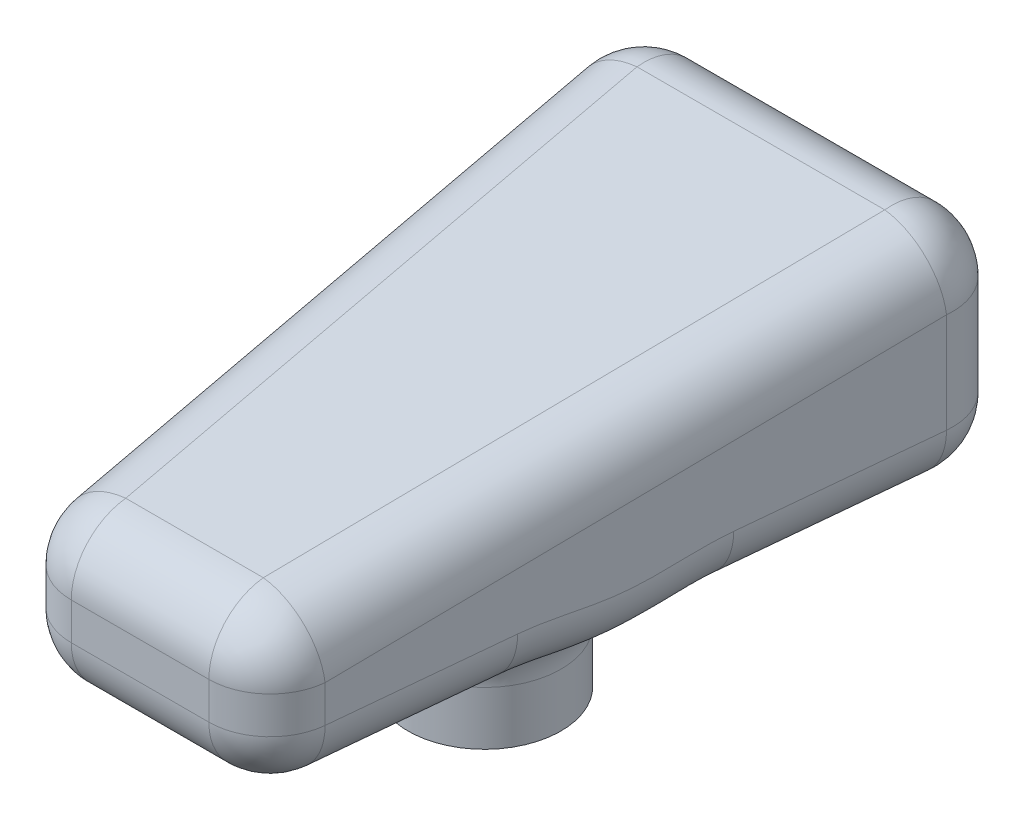
SolidWorks part; units mm, degrees
ref_plane "Front Plane" through (0, 0, 0) normal (0, 0, 1) x (1, 0, 0)
ref_plane "Top Plane" through (0, 0, 0) normal (0, 1, 0) x (1, 0, 0)
ref_plane "Right Plane" through (0, 0, 0) normal (1, 0, 0) x (0, 0, -1)
sketch "Sketch1" plane through (0, 0, 0) normal (0, 1, 0) x (1, 0, 0)
  circle A0 centre (0, 0) radius 25.4
  dimension "D1" = 50.8
extrude "Boss-Extrude1" add sketch "Sketch1" along normal blind 38.1
sketch "Sketch2" plane through (0, 38.1, 0) normal (0, 1, 0) x (1, 0, 0)
  line L1 (-63.5, -114.3) -> (63.5, -114.3)
  line L2 (-63.5, -114.3) -> (-63.5, 114.3)
  line L3 (-63.5, 114.3) -> (63.5, 114.3)
  line L4 (63.5, -114.3) -> (63.5, 114.3)
  line L5 (-63.5, -114.3) -> (63.5, 114.3) construction
  line L6 (-63.5, 114.3) -> (63.5, -114.3) construction
  point P0 (0, 0)
  dimension "D1" = 228.6
  dimension "D2" = 127
extrude "Boss-Extrude2" add sketch "Sketch2" along normal blind 76.2
fillet "Fillet1" radius 20.32 1 edges at (0, 38.1, 25.4)
sketch "Sketch3" plane through (63.5, 0, 0) normal (1, 0, 0) x (0, 0, -1)
  line L0 (114.3, 114.3) -> (-114.3, 114.3)
  line L1 (-114.3, 114.3) -> (-114.3, 88.9)
  line L2 (-114.3, 114.3) -> (-114.3, 38.1) construction
  line L3 (-114.3, 88.9) -> (114.3, 114.3)
  dimension "D1" = 25.4
extrude "Cut-Extrude1" cut sketch "Sketch3" against normal up to next
sketch "Sketch5" plane through (0, 38.1, 0) normal (0, -1, 0) x (1, 0, 0)
  line L0 (63.5, 114.3) -> (63.5, -114.3)
  line L1 (63.5, -114.3) -> (41.275, 114.3)
  line L2 (-63.5, 114.3) -> (63.5, 114.3) construction
  line L3 (41.275, 114.3) -> (63.5, 114.3)
  line L4 (-63.5, -114.3) -> (-63.5, 114.3)
  line L5 (-63.5, 114.3) -> (-41.275, 114.3)
  line L6 (-41.275, 114.3) -> (-63.5, -114.3)
  dimension "D1" = 22.225
  dimension "D2" = 22.225
extrude "Cut-Extrude3" cut sketch "Sketch5" against normal up to next
fillet "Fillet2" radius 20.32 12 edges at (41.275, 63.5, 114.3) (-41.275, 63.5, 114.3) (-63.5, 76.2, -114.3) (63.5, 76.2, -114.3) (52.3875, 38.1, 0) (0, 38.1, -114.3) (-52.3875, 38.1, 0) (0, 38.1, 114.3) (0, 88.9, 114.3) (0, 114.3, -114.3) (52.3875, 101.6, 0) (-52.3875, 101.6, 0)
